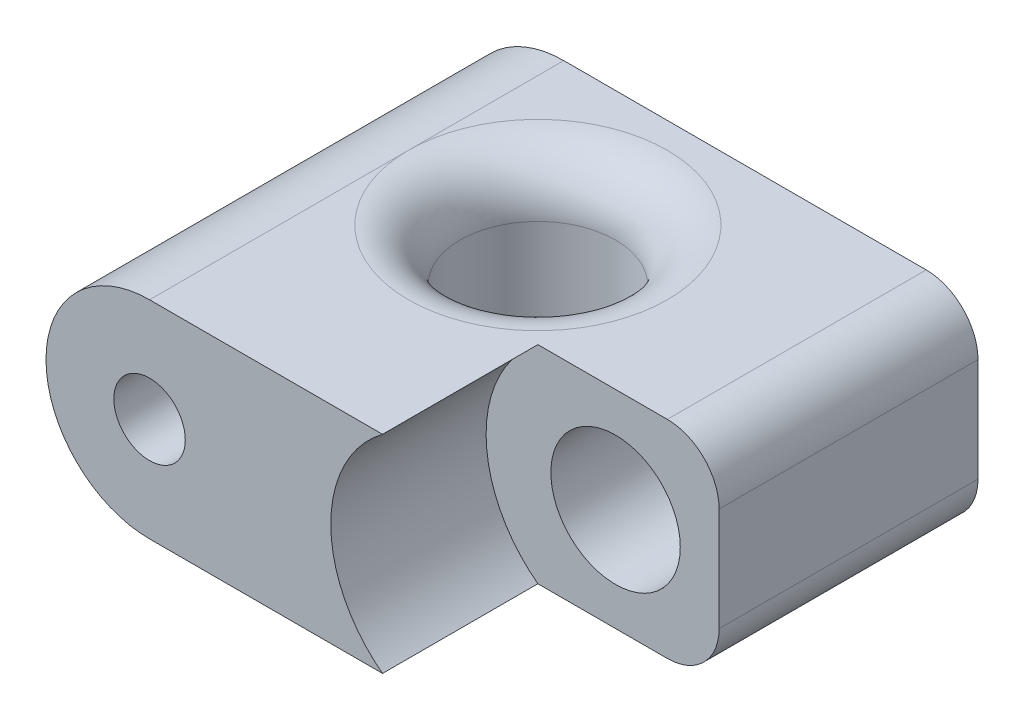
SolidWorks part; units mm, degrees
ref_plane "정면" through (0, 0, 0) normal (0, 0, 1) x (1, 0, 0)
ref_plane "윗면" through (0, 0, 0) normal (0, 1, 0) x (1, 0, 0)
ref_plane "우측면" through (0, 0, 0) normal (1, 0, 0) x (0, 0, -1)
sketch "Sketch2" plane through (0, 0, 0) normal (0, 0, 1) x (1, 0, 0)
  line L1 (0, 0) -> (-10.16, 0)
  line L2 (0, 0) -> (0, 10.16)
  line L3 (0, 10.16) -> (-10.16, 10.16)
  line L4 (-10.16, 0) -> (-10.16, 10.16)
  dimension "D1" = 10.16
  dimension "D2" = 10.16
extrude "Extrude2" add sketch "Sketch2" along normal blind 20.32
fillet "Fillet1" radius 2.54 2 edges at (0, 0, 10.16) (0, 10.16, 10.16)
sketch "Sketch5" plane through (-10.16, 0, 0) normal (-1, 0, 0) x (0, 0, 1)
  line L1 (0, 10.16) -> (20.32, 10.16)
  line L2 (0, 10.16) -> (0, 0)
  line L3 (0, 0) -> (20.32, 0)
  line L4 (20.32, 10.16) -> (20.32, 0)
extrude "Extrude3" add sketch "Sketch5" along normal blind 15.24
fillet "Fillet3" radius 5.08 2 edges at (-25.4, 0, 10.16) (-25.4, 10.16, 10.16)
sketch "Sketch9" plane through (0, 10.16, 0) normal (0, 1, 0) x (-1, 0, 0)
  line L1 (20.32, 0) -> (2.54, 0)
  line L2 (20.32, 0) -> (20.32, 20.32)
  line L3 (20.32, 20.32) -> (2.54, 20.32)
  line L4 (2.54, 0) -> (2.54, 20.32)
  circle A0 centre (13.97, 7.62) radius 3.81
  dimension "D1" = 7.62
  dimension "D2" = 12.7
  dimension "D3" = 6.35
extrude "Cut-Extrude1" cut sketch "Sketch9" against normal through all contours A0
fillet "Fillet4" radius 2.54 2 edges at (-17.78, 0, 7.62) (-17.78, 10.16, 7.62)
sketch "Sketch10" plane through (0, 0, 20.32) normal (0, 0, 1) x (1, 0, 0)
  line L2 (0, 2.54) -> (0, 7.62) construction
  line L3 (-2.54, 10.16) -> (-20.32, 10.16) construction
  circle A0 centre (-5.08, 5.08) radius 6.35
  dimension "D1" = 12.7
  dimension "D2" = 5.08
  dimension "D3" = 5.08
extrude "Cut-Extrude2" cut sketch "Sketch10" against normal blind 7.62
hole_wizard "1/4 (0.25) Diameter Hole1" positions "3DSketch1" profile "Sketch11" hole size "1/4" standard "Ansi Inch" end condition through all
sketch3d "3DSketch1"
  line L2 (-8.89, 0, 12.7) -> (-2.54, 0, 12.7) construction
  line L3 (0, 2.54, 12.7) -> (0, 7.62, 12.7) construction
  point P21 (-5.08, 5.048, 12.7)
  dimension "D1" = 5.048
  dimension "D2" = 5.08
sketch "Sketch11" plane through (-5.08, 5.048, 12.7) normal (1, 0, 0) x (0, -1, 0)
  line L0 (0, 0) -> (0, 12.7)
  line L1 (0, 12.7) -> (3.175, 12.7)
  line L2 (3.175, 12.7) -> (3.175, 0)
  line L5 (3.175, 0) -> (0, 0)
  line L11 (0, -6.35) -> (0, 107.95) construction
  dimension "Thru Hole Dia." = 6.35
  dimension "Thru Hole Depth" = 12.7
hole_wizard "#6-32 Tapped Hole1" positions "3DSketch2" profile "Sketch12" tap size "#6-32" standard "Ansi Inch" end condition through all
sketch3d "3DSketch2"
  arc A0 (-25.4, 5.08, 20.32) -> (-20.32, 0, 20.32) centre (-20.32, 5.08, 20.32) ccw construction
  point P0 (-20.32, 5.08, 20.32)
  point P7 (-20.32, 5.08, 25.4)
sketch "Sketch12" plane through (-20.32, 5.08, 20.32) normal (1, 0, 0) x (0, -1, 0)
  line L0 (0, 0) -> (0, 20.32)
  line L1 (0, 20.32) -> (1.7526, 20.32)
  line L2 (1.7526, 20.32) -> (1.7526, 0)
  line L5 (1.7526, 0) -> (0, 0)
  line L11 (0, -6.35) -> (0, 107.95) construction
  dimension "Thread Major Dia." = 3.5052
  dimension "Thru Tap Drill Depth" = 20.32
